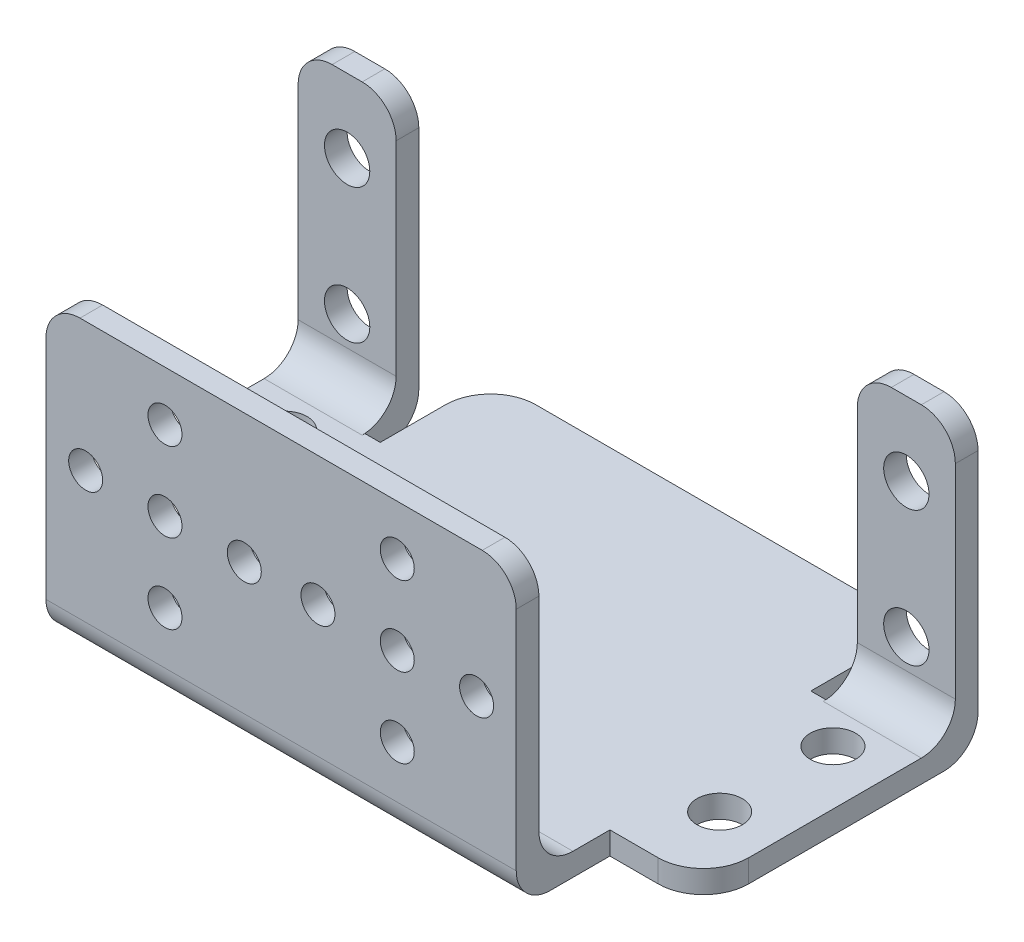
SolidWorks part; units mm, degrees
ref_plane "前视基准面" through (0, 0, 0) normal (0, 0, 1) x (1, 0, 0)
ref_plane "上视基准面" through (0, 0, 0) normal (0, 1, 0) x (1, 0, 0)
ref_plane "右视基准面" through (0, 0, 0) normal (1, 0, 0) x (0, 0, -1)
sketch "草图1" plane through (0, 0, 0) normal (0, 1, 0) x (1, 0, 0)
  line L0 (20.75, 0) -> (-20.75, 0)
  line L1 (-20.75, 0) -> (-20.75, 6.2662)
  line L2 (-20.75, 6.2662) -> (-25, 6.2662)
  line L3 (-29, 10.2662) -> (-29, 28.5)
  line L4 (-29, 28.5) -> (-20.3494, 28.5)
  line L5 (-20.3494, 28.5) -> (-20.3494, 25.7465)
  line L6 (-20.3494, 25.7465) -> (-19, 25.7465)
  line L7 (-19, 25.7465) -> (-19, 31.49)
  line L8 (-15, 35.49) -> (15, 35.49)
  line L9 (0, 35.49) -> (0, 0) construction
  line L10 (19, 25.7465) -> (19, 31.49)
  line L11 (20.3494, 25.7465) -> (19, 25.7465)
  line L12 (20.3494, 28.5) -> (20.3494, 25.7465)
  line L13 (29, 28.5) -> (20.3494, 28.5)
  line L14 (20.75, 6.2662) -> (25, 6.2662)
  line L15 (20.75, 0) -> (20.75, 6.2662)
  line L16 (29, 10.2662) -> (29, 28.5)
  circle A0 centre (-24.2, 22.5) radius 2
  circle A1 centre (-24.2, 12.5) radius 2
  arc A2 (-15, 35.49) -> (-19, 31.49) centre (-15, 31.49) ccw
  arc A3 (-29, 10.2662) -> (-25, 6.2662) centre (-25, 10.2662) ccw
  arc A4 (29, 10.2662) -> (25, 6.2662) centre (25, 10.2662) cw
  arc A5 (15, 35.49) -> (19, 31.49) centre (15, 31.49) cw
  circle A6 centre (24.2, 12.5) radius 2
  circle A7 centre (24.2, 22.5) radius 2
  dimension "D3" = 4
  dimension "D6" = 10
  dimension "D7" = 12.5
  dimension "D8" = 24.2
  dimension "D9" = 4
  dimension "D10" = 4
  dimension "D1" = 29
  dimension "D2" = 19
  dimension "D4" = 35.49
  dimension "D5" = 28.5
  dimension "D11" = 41.5
extrude "凸台-拉伸1" add sketch "草图1" along normal blind 2 contours A4 L14 L15 L0 L1 L2 A3 L3 L4 L5 L6 L7 A2 L8 A5 L10 L11 L12 L13 L16
sketch "草图3" plane through (0, 0, 0) normal (0, 1, 0) x (1, 0, 0)
  line L0 (20.75, 0) -> (20.75, 6.2662) construction
  line L1 (-29, 28.5) -> (-20.3494, 28.5)
  line L2 (-29, 28.5) -> (-29, 30.5)
  line L3 (-29, 30.5) -> (-20.3494, 30.5)
  line L4 (-20.3494, 28.5) -> (-20.3494, 30.5)
  line L5 (20.3494, 28.5) -> (29, 28.5)
  line L6 (20.3494, 28.5) -> (20.3494, 30.5)
  line L7 (20.3494, 30.5) -> (29, 30.5)
  line L8 (29, 28.5) -> (29, 30.5)
  line L9 (-20.75, 0) -> (20.75, 0)
  line L10 (-20.75, 0) -> (-20.75, -2)
  line L11 (-20.75, -2) -> (20.75, -2)
  line L12 (20.75, 0) -> (20.75, -2)
  dimension "D1" = 2
  dimension "D2" = 2
  dimension "D3" = 2
extrude "凸台-拉伸2" add sketch "草图3" along normal blind 26
sketch "草图4" plane through (0, 0, -28.5) normal (0, 0, 1) x (1, 0, 0)
  line L0 (-29, 26) -> (-20.3494, 26) construction
  line L6 (-24.6747, 27.3884) -> (-24.6747, 3.7759) construction
  circle A0 centre (-24.6747, 19.5) radius 2
  circle A1 centre (-24.6747, 7.6) radius 2
  dimension "D1" = 4
  dimension "D2" = 4
  dimension "D3" = 11.9
  dimension "D4" = 6.5
extrude "切除-拉伸1" cut sketch "草图4" against normal up to next
ref_plane "基准面1" through (0, 0, 0) normal (-1, 0, 0) x (0, 0, 1)
sketch "草图5" plane through (0, 0, 2) normal (0, 0, 1) x (1, 0, 0)
  line L1 (-20.75, 26) -> (-20.75, 0) construction
  line L2 (-20.75, 26) -> (20.75, 26) construction
  circle A0 centre (-10.25, 14.6) radius 1.5
  circle A1 centre (-10.25, 21.6) radius 1.5
  circle A2 centre (-3.25, 14.6) radius 1.5
  circle A3 centre (-10.25, 7.6) radius 1.5
  circle A4 centre (-17.25, 14.6) radius 1.5
  point P13 (-10.25, 14.6)
  dimension "D1" = 3
  dimension "D2" = 3
  dimension "D5" = 10.5
  dimension "D6" = 11.4
  dimension "D3" = 7
  dimension "D4" = 4
extrude "切除-拉伸2" cut sketch "草图5" against normal up to next
mirror "镜向2" about plane through (0, 0, 0) normal (-1, 0, 0) of "切除-拉伸1", "切除-拉伸2"
fillet "圆角1" radius 3 12 edges at (0, 2, 0) (0, 0, 2) (24.6747, 2, -28.5) (24.6747, 0, -30.5) (-24.6747, 2, -28.5) (-24.6747, 0, -30.5) (-20.75, 26, 1) (20.75, 26, 1) (29, 26, -29.5) (20.3494, 26, -29.5) (-20.3494, 26, -29.5) (-29, 26, -29.5)
